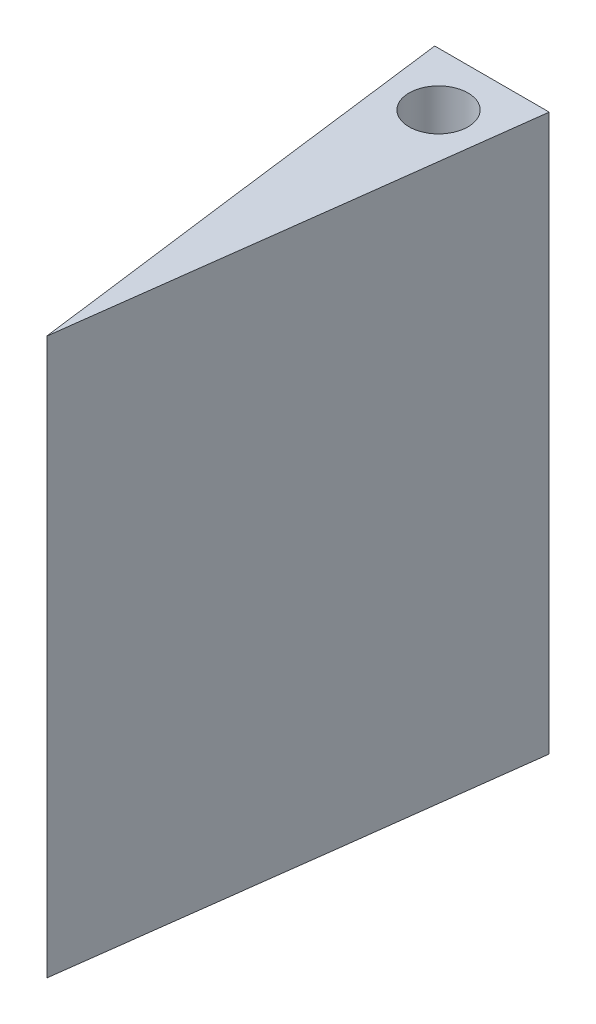
SolidWorks part; units mm, degrees
ref_plane "Front Plane" through (0, 0, 0) normal (0, 0, 1) x (1, 0, 0)
ref_plane "Top Plane" through (0, 0, 0) normal (0, 1, 0) x (1, 0, 0)
ref_plane "Right Plane" through (0, 0, 0) normal (1, 0, 0) x (0, 0, -1)
sketch "Sketch1" plane through (0, 0, 0) normal (0, 1, 0) x (1, 0, 0)
  line L0 (1.1081, 1.7265) -> (-45.0799, 1.7265) construction
  line L1 (-45.0799, 1.7265) -> (-45.0799, -11.2275) construction
  line L2 (-45.0799, -11.2275) -> (43.7517, -11.2275) construction
  line L3 (1.1081, 103.3269) -> (1.1081, -99.8738) construction
  line L4 (-45.0799, -11.2275) -> (-45.0799, -20.7525) construction
  line L5 (-28.2049, 1.7265) -> (-28.2049, -3.6075) construction
  line L6 (-9.9553, -3.6075) -> (-6.7697, -3.6075)
  line L7 (-28.2049, -3.6075) -> (-9.9553, -3.6075) construction
  line L8 (-6.7697, -3.6075) -> (1.1081, -3.6075) construction
  line L9 (8.9859, -3.6075) -> (12.1715, -3.6075)
  line L10 (12.1715, -3.6075) -> (18.1346, -3.6075) construction
  line L11 (12.1715, -3.6075) -> (18.1346, -3.6075) construction
  line L12 (18.1346, -3.6075) -> (29.3788, -3.6075) construction
  line L13 (1.1081, -3.6075) -> (8.9859, -3.6075) construction
  line L14 (-6.7697, -3.6075) -> (8.9859, -3.6075)
  circle A0 centre (1.1081, -11.3265) radius 1.9844 construction
  circle A1 centre (1.1081, -11.3265) radius 1.9844
  spline S0 degree 3 poles (1.1081, -99.8738) (4.5273, -73.5318) (7.9866, -47.1872) (10.6029, -20.7525) knots 0 0 0 0 0.38497 0.38497 0.38497 0.38497
  spline S3 degree 3 poles (1.1081, -99.8738) (-2.3112, -73.5318) (-5.7704, -47.1872) (-8.3867, -20.7525) knots 0 0 0 0 0.38497 0.38497 0.38497 0.38497
  spline S4 degree 3 poles (10.6029, -20.7525) (11.1, -15.7302) (11.6306, -10.016) (12.114, -4.2968) (12.1715, -3.6075) knots 0.38497 0.38497 0.38497 0.38497 0.458109 0.468132 0.468132 0.468132 0.468132
  spline S5 degree 3 poles (-8.3867, -20.7525) (-8.8838, -15.7302) (-9.4144, -10.016) (-9.8978, -4.2968) (-9.9553, -3.6075) knots 0.38497 0.38497 0.38497 0.38497 0.458109 0.468132 0.468132 0.468132 0.468132
  spline S8 degree 3 poles (12.1715, -3.6075) (12.8364, 4.367) (14.1908, 23.6726) (14.0058, 48.0803) (13.0188, 67.5796) (11.3266, 78.9472) (9.5869, 86.9693) (8.1237, 93.6397) (6.4505, 97.563) (4.8164, 101.3994) (2.3437, 102.5279) (1.1081, 103.3269) knots 0.468132 0.468132 0.468132 0.468132 0.584075 0.748482 0.821537 0.866809 0.914778 0.94069 0.965303 0.976863 1 1 1 1 construction
  spline S9 degree 3 poles (1.1081, 99.6196) (1.2739, 99.518) (1.6209, 99.2976) (2.0134, 99.0137) (2.3095, 98.7539) (2.4667, 98.5788) (2.6076, 98.3713) (2.8163, 97.9774) (3.0534, 97.4394) (3.4327, 96.5453) (3.8774, 95.496) (4.541, 93.8448) (5.2023, 91.9048) (5.8236, 89.3366) (6.4213, 86.5662) (7.0145, 83.8293) (7.767, 80.1951) (8.6007, 75.6781) (9.6391, 68.4081) (10.3034, 59.2354) (10.6788, 47.9926) (10.8555, 36.7918) (10.7415, 25.5951) (10.3009, 14.4244) (9.6564, 4.6878) (9.1767, -1.3266) (8.9859, -3.6075) knots 0.118744 0.118744 0.118744 0.118744 0.122149 0.125554 0.12896 0.132365 0.13577 0.139175 0.142581 0.145986 0.152796 0.159607 0.173228 0.186849 0.20047 0.214091 0.227711 0.254953 0.282195 0.336679 0.391163 0.445646 0.50013 0.554614 0.609098 0.642376 0.642376 0.642376 0.642376 construction
  spline S10 degree 3 poles (-7.1984, 1.7265) (-7.237, 2.2289) (-7.5577, 6.4638) (-8.0847, 14.4244) (-8.5253, 25.5951) (-8.6393, 36.7918) (-8.4626, 47.9926) (-8.0872, 59.2354) (-7.4229, 68.4081) (-6.3845, 75.6781) (-5.5508, 80.1951) (-4.7983, 83.8293) (-4.2051, 86.5662) (-3.6074, 89.3366) (-2.9861, 91.9048) (-2.3248, 93.8448) (-1.6612, 95.496) (-1.2165, 96.5453) (-0.8372, 97.4394) (-0.6001, 97.9774) (-0.3914, 98.3713) (-0.2505, 98.5788) (-0.0933, 98.7539) (0.2028, 99.0137) (0.5953, 99.2976) (0.9423, 99.518) (1.1081, 99.6196) knots 0.492798 0.492798 0.492798 0.492798 0.50013 0.554614 0.609098 0.663581 0.718065 0.772549 0.827033 0.854275 0.881516 0.895137 0.908758 0.922379 0.936 0.949621 0.956432 0.963242 0.966647 0.970053 0.973458 0.976863 0.980268 0.983674 0.987079 0.990484 0.990484 0.990484 0.990484 construction
  spline S11 degree 3 poles (-10.3826, 1.7265) (-10.8572, 7.9268) (-11.9611, 25.4575) (-11.7896, 48.0803) (-10.8026, 67.5796) (-9.1104, 78.9472) (-7.3707, 86.9693) (-5.9075, 93.6397) (-4.2343, 97.563) (-2.6002, 101.3994) (-0.1276, 102.5279) (1.1081, 103.3269) knots 0.493976 0.493976 0.493976 0.493976 0.584075 0.748482 0.821537 0.866809 0.914778 0.94069 0.965303 0.976863 1 1 1 1 construction
  spline S12 degree 3 poles (-9.9553, -3.6075) (-10.1035, -1.8299) (-10.2465, -0.0519) (-10.3826, 1.7265) knots 0.468132 0.468132 0.468132 0.468132 0.493976 0.493976 0.493976 0.493976 construction
  spline S13 degree 3 poles (-6.7697, -3.6075) (-6.9185, -1.8292) (-7.0618, -0.0511) (-7.1984, 1.7265) knots 0.466852 0.466852 0.466852 0.466852 0.492798 0.492798 0.492798 0.492798 construction
  dimension "D4" = 3.9688
  dimension "D1" = 12.954
  dimension "D2" = 9.525
  dimension "D3" = 5.334
extrude "Boss-Extrude1" add sketch "Sketch1" along normal blind 169.8727
sketch "Sketch2" plane through (0, 169.8727, 0) normal (0, 1, 0) x (1, 0, 0)
  line L1 (-9.9553, -3.6075) -> (25.8085, -3.6075)
  line L2 (-9.9553, -3.6075) -> (-9.9553, -26.3125)
  line L3 (-9.9553, -26.3125) -> (25.8085, -26.3125)
  line L4 (25.8085, -3.6075) -> (25.8085, -26.3125)
  circle A0 centre (1.1081, -11.3265) radius 1.9844 construction
  dimension "D1" = 14.986
extrude "Cut-Extrude1" cut sketch "Sketch2" against normal blind 23.0581
extrude "Cut-Extrude2" cut sketch "Sketch2<2>" along normal blind 23.0581 from surface starting at face at (-1.1046, 0, 29.7187)
sketch "Sketch2<2>" plane through (0, 169.8727, 0) normal (0, 1, 0) x (1, 0, 0) same geometry as "Sketch2"
fillet "Fillet1" radius 7.62 6 edges at (-7.8242, 11.5291, 26.3125) (10.0403, 11.5291, 26.3125) (12.1715, 84.9363, 3.6075) (-7.8242, 158.3436, 26.3125) (10.0403, 158.3436, 26.3125)
sketch "Sketch6" plane through (0, 0, 0) normal (0, -1, 0) x (1, 0, 0)
  line L0 (1.1081, 3.6075) -> (1.1081, 99.8738) construction
  line L1 (-1.6395, 3.6075) -> (3.8557, 3.6075) construction
  line L2 (-6.9254, 34.7606) -> (9.1416, 34.7606) construction
  circle A0 centre (1.1081, 71.9338) radius 2.1
  circle A1 centre (1.1081, 34.7606) radius 2.1
  dimension "D1" = 4.2
  dimension "D2" = 27.94
extrude "Cut-Extrude3" cut sketch "Sketch6" against normal through all both and the other way through all
sketch "Sketch7" plane through (0, 0, 0) normal (1, 0, 0) x (0, 0, -1)
  line L0 (-3.6075, 146.8145) -> (-3.6075, 23.0581) construction
  line L1 (-99.8738, 0) -> (-3.6075, 0)
  line L2 (-99.8738, 0) -> (-99.8738, 79.911)
  line L3 (-99.8738, 79.911) -> (-3.6075, 79.911)
  line L4 (-3.6075, 0) -> (-3.6075, 79.911)
  line L6 (-99.8738, 169.8727) -> (-3.6075, 169.8727)
  line L7 (-99.8738, 169.8727) -> (-99.8738, 119.5579)
  line L8 (-99.8738, 119.5579) -> (-3.6075, 119.5579)
  line L9 (-3.6075, 169.8727) -> (-3.6075, 119.5579)
  dimension "D2" = 39.6469
extrude "Cut-Extrude4" cut sketch "Sketch7" against normal through all both and the other way through all
sketch "Sketch8" plane through (0, 79.911, 0) normal (0, -1, 0) x (1, 0, 0)
  line L1 (-35.7382, 68.1238) -> (19.5961, 68.1238)
  line L2 (-35.7382, 68.1238) -> (-35.7382, -22.5784)
  line L3 (-35.7382, -22.5784) -> (19.5961, -22.5784)
  line L4 (19.5961, 68.1238) -> (19.5961, -22.5784)
  dimension "D2" = 31.75
extrude "Cut-Extrude5" cut sketch "Sketch8" against normal through all both
